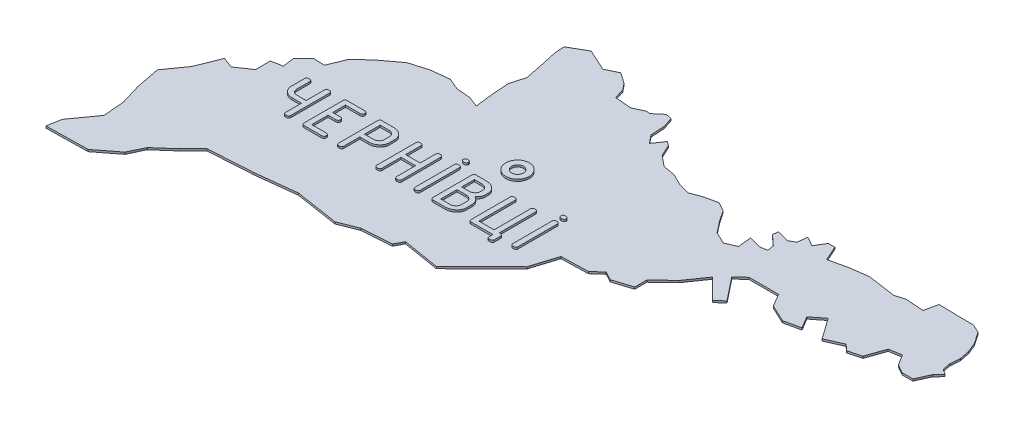
SolidWorks part; units mm, degrees
ref_plane "Спереди" through (0, 0, 0) normal (0, 0, 1) x (1, 0, 0)
ref_plane "Сверху" through (0, 0, 0) normal (0, 1, 0) x (1, 0, 0)
ref_plane "Справа" through (0, 0, 0) normal (1, 0, 0) x (0, 0, -1)
sketch "Эскиз1" plane through (0, 0, 0) normal (0, 1, 0) x (1, 0, 0)
  line B0 (-5205.415, 3609.1673) -> (-5161.2724, 3670.7877)
  line B1 (-5161.2724, 3670.7877) -> (-5165.8164, 3725.3443)
  line B2 (-5165.8164, 3725.3443) -> (-5181.3993, 3776.5482)
  line B3 (-5181.3993, 3776.5482) -> (-5193.7234, 3839.5402)
  line B4 (-5193.7234, 3839.5402) -> (-5157.3862, 3890.7949)
  line B5 (-5157.3862, 3890.7949) -> (-5133.3578, 3950.5103)
  line B6 (-5133.3578, 3950.5103) -> (-5106.1188, 3940.1166)
  line B7 (-5106.1188, 3940.1166) -> (-5069.1288, 3965.4251)
  line B8 (-5069.1288, 3965.4251) -> (-5069.1288, 4003.0603)
  line B9 (-5069.1288, 4003.0603) -> (-5053.5586, 4006.3115)
  line B10 (-5053.5586, 4006.3115) -> (-5041.2193, 4008.2699)
  line B11 (-5041.2193, 4008.2699) -> (-5045.1055, 4038.7626)
  line B12 (-5045.1055, 4038.7626) -> (-5019.1467, 4064.0711)
  line B13 (-5019.1467, 4064.0711) -> (-4990.6022, 4062.7757)
  line B14 (-4990.6022, 4062.7757) -> (-4973.0711, 4106.8879)
  line B15 (-4973.0711, 4106.8879) -> (-4937.3866, 4139.311)
  line B16 (-4937.3866, 4139.311) -> (-4891.3237, 4173.7178)
  line B17 (-4891.3237, 4173.7178) -> (-4845.238, 4187.3627)
  line B18 (-4845.238, 4187.3627) -> (-4799.17, 4192.5469)
  line B19 (-4799.17, 4192.5469) -> (-4769.9651, 4180.2228)
  line B20 (-4769.9651, 4180.2228) -> (-4734.2781, 4176.997)
  line B21 (-4734.2781, 4176.997) -> (-4707.0188, 4166.6033)
  line B22 (-4707.0188, 4166.6033) -> (-4712.2105, 4211.3784)
  line B23 (-4712.2105, 4211.3784) -> (-4715.4592, 4257.4464)
  line B24 (-4715.4592, 4257.4464) -> (-4705.063, 4294.4186)
  line B25 (-4705.063, 4294.4186) -> (-4714.1587, 4339.1938)
  line B26 (-4714.1587, 4339.1938) -> (-4723.8818, 4383.3313)
  line B27 (-4723.8818, 4383.3313) -> (-4725.8453, 4409.3028)
  line B28 (-4725.8453, 4409.3028) -> (-4681.7153, 4434.6114)
  line B29 (-4681.7153, 4434.6114) -> (-4626.5617, 4409.3028)
  line B30 (-4626.5617, 4409.3028) -> (-4596.0411, 4424.2177)
  line B31 (-4596.0411, 4424.2177) -> (-4568.7844, 4405.4141)
  line B32 (-4568.7844, 4405.4141) -> (-4555.1446, 4388.5409)
  line B33 (-4555.1446, 4388.5409) -> (-4548.0122, 4363.2069)
  line B34 (-4548.0122, 4363.2069) -> (-4505.8432, 4359.3182)
  line B35 (-4505.8432, 4359.3182) -> (-4479.8844, 4371.6677)
  line B36 (-4479.8844, 4371.6677) -> (-4468.2156, 4371.6677)
  line B37 (-4468.2156, 4371.6677) -> (-4446.1532, 4390.4713)
  line B38 (-4446.1532, 4390.4713) -> (-4430.5677, 4387.2455)
  line B39 (-4430.5677, 4387.2455) -> (-4422.1451, 4361.2765)
  line B40 (-4422.1451, 4361.2765) -> (-4420.1969, 4325.5743)
  line B41 (-4420.1969, 4325.5743) -> (-4403.3237, 4304.8123)
  line B42 (-4403.3237, 4304.8123) -> (-4384.5074, 4332.0792)
  line B43 (-4384.5074, 4332.0792) -> (-4374.1061, 4323.6413)
  line B44 (-4374.1061, 4323.6413) -> (-4360.5044, 4294.4186)
  line B45 (-4360.5044, 4294.4186) -> (-4333.2375, 4272.3638)
  line B46 (-4333.2375, 4272.3638) -> (-4302.7194, 4267.1797)
  line B47 (-4302.7194, 4267.1797) -> (-4275.4779, 4253.5348)
  line B48 (-4275.4779, 4253.5348) -> (-4244.3248, 4245.0969)
  line B49 (-4244.3248, 4245.0969) -> (-4215.765, 4255.516)
  line B50 (-4215.765, 4255.516) -> (-4183.314, 4262.6305)
  line B51 (-4183.314, 4262.6305) -> (-4160.6216, 4250.3065)
  line B52 (-4160.6216, 4250.3065) -> (-4142.453, 4223.0396)
  line B53 (-4142.453, 4223.0396) -> (-4119.7352, 4193.8702)
  line B54 (-4119.7352, 4193.8702) -> (-4089.2425, 4178.9274)
  line B55 (-4089.2425, 4178.9274) -> (-4061.9782, 4190.6165)
  line B56 (-4061.9782, 4190.6165) -> (-4065.2294, 4224.9979)
  line B57 (-4065.2294, 4224.9979) -> (-4034.7367, 4216.56)
  line B58 (-4034.7367, 4216.56) -> (-4015.8822, 4219.8138)
  line B59 (-4015.8822, 4219.8138) -> (-4019.136, 4236.687)
  line B60 (-4019.136, 4236.687) -> (-4045.1049, 4260.6747)
  line B61 (-4045.1049, 4260.6747) -> (-4043.1491, 4274.3196)
  line B62 (-4043.1491, 4274.3196) -> (-4012.6564, 4265.8843)
  line B63 (-4012.6564, 4265.8843) -> (-3997.0786, 4274.3196)
  line B64 (-3997.0786, 4274.3196) -> (-3993.8249, 4299.6282)
  line B65 (-3993.8249, 4299.6282) -> (-3969.8117, 4286.0087)
  line B66 (-3969.8117, 4286.0087) -> (-3954.2364, 4311.9777)
  line B67 (-3954.2364, 4311.9777) -> (-3937.3886, 4311.9777)
  line B68 (-3937.3886, 4311.9777) -> (-3920.49, 4274.3196)
  line B69 (-3920.49, 4274.3196) -> (-3874.4449, 4284.7133)
  line B70 (-3874.4449, 4284.7133) -> (-3828.3515, 4291.1674)
  line B71 (-3828.3515, 4291.1674) -> (-3792.0143, 4286.0087)
  line B72 (-3792.0143, 4286.0087) -> (-3756.3374, 4280.7992)
  line B73 (-3756.3374, 4280.7992) -> (-3731.0263, 4287.9391)
  line B74 (-3731.0263, 4287.9391) -> (-3684.9583, 4284.7133)
  line B75 (-3684.9583, 4284.7133) -> (-3677.793, 4318.4572)
  line B76 (-3677.793, 4318.4572) -> (-3621.3542, 4317.1364)
  line B77 (-3621.3542, 4317.1364) -> (-3588.9057, 4317.1364)
  line B78 (-3588.9057, 4317.1364) -> (-3566.8229, 4306.7681)
  line B79 (-3566.8229, 4306.7681) -> (-3546.7239, 4277.548)
  line B80 (-3546.7239, 4277.548) -> (-3536.3302, 4252.2623)
  line B81 (-3536.3302, 4252.2623) -> (-3531.1715, 4226.2933)
  line B82 (-3531.1715, 4226.2933) -> (-3533.1019, 4200.9847)
  line B83 (-3533.1019, 4200.9847) -> (-3529.1903, 4180.2228)
  line B84 (-3529.1903, 4180.2228) -> (-3515.5683, 4171.7874)
  line B85 (-3515.5683, 4171.7874) -> (-3531.1715, 4154.9142)
  line B86 (-3531.1715, 4154.9142) -> (-3546.7239, 4120.5074)
  line B87 (-3546.7239, 4120.5074) -> (-3573.9629, 4120.5074)
  line B88 (-3573.9629, 4120.5074) -> (-3596.0202, 4132.8315)
  line B89 (-3596.0202, 4132.8315) -> (-3612.9189, 4160.0984)
  line B90 (-3612.9189, 4160.0984) -> (-3644.0466, 4154.9142)
  line B91 (-3644.0466, 4154.9142) -> (-3660.9198, 4106.8879)
  line B92 (-3660.9198, 4106.8879) -> (-3693.3683, 4098.4526)
  line B93 (-3693.3683, 4098.4526) -> (-3708.9715, 4112.0974)
  line B94 (-3708.9715, 4112.0974) -> (-3751.1279, 4093.2938)
  line B95 (-3751.1279, 4093.2938) -> (-3788.7859, 4146.4789)
  line B96 (-3788.7859, 4146.4789) -> (-3819.2786, 4122.4657)
  line B97 (-3819.2786, 4122.4657) -> (-3801.0846, 4091.9476)
  line B98 (-3801.0846, 4091.9476) -> (-3841.971, 4082.8747)
  line B99 (-3841.971, 4082.8747) -> (-3886.1086, 4103.6342)
  line B100 (-3886.1086, 4103.6342) -> (-3904.9401, 4136.0852)
  line B101 (-3904.9401, 4136.0852) -> (-3980.2054, 4136.0852)
  line B102 (-3980.2054, 4136.0852) -> (-4003.5582, 4115.3232)
  line B103 (-4003.5582, 4115.3232) -> (-3956.1922, 4055.6078)
  line B104 (-3956.1922, 4055.6078) -> (-3976.3167, 4038.7626)
  line B105 (-3976.3167, 4038.7626) -> (-4027.5713, 4090.0147)
  line B106 (-4027.5713, 4090.0147) -> (-4061.9782, 4040.693)
  line B107 (-4061.9782, 4040.693) -> (-4104.7949, 3999.8066)
  line B108 (-4104.7949, 3999.8066) -> (-4104.7949, 3968.6535)
  line B109 (-4104.7949, 3968.6535) -> (-4152.1609, 3953.7361)
  line B110 (-4152.1609, 3953.7361) -> (-4174.2436, 3965.4251)
  line B111 (-4174.2436, 3965.4251) -> (-4198.2568, 3944.0053)
  line B112 (-4198.2568, 3944.0053) -> (-4266.3821, 3942.0724)
  line B113 (-4266.3821, 3942.0724) -> (-4287.1415, 3875.8774)
  line B114 (-4287.1415, 3875.8774) -> (-4403.3237, 3760.9958)
  line B115 (-4403.3237, 3760.9958) -> (-4497.4154, 3776.5482)
  line B116 (-4497.4154, 3776.5482) -> (-4509.0918, 3754.5162)
  line B117 (-4509.0918, 3754.5162) -> (-4584.3571, 3749.3321)
  line B118 (-4584.3571, 3749.3321) -> (-4631.7433, 3730.5031)
  line B119 (-4631.7433, 3730.5031) -> (-4741.4129, 3747.3763)
  line B120 (-4741.4129, 3747.3763) -> (-4843.2923, 3735.7126)
  line B121 (-4843.2923, 3735.7126) -> (-4956.1877, 3728.5727)
  line B122 (-4956.1877, 3728.5727) -> (-4991.9026, 3692.8704)
  line B123 (-4991.9026, 3692.8704) -> (-5034.727, 3655.2099)
  line B124 (-5034.727, 3655.2099) -> (-5053.5586, 3616.3072)
  line B125 (-5053.5586, 3616.3072) -> (-5106.1188, 3575.4208)
  line B126 (-5106.1188, 3575.4208) -> (-5211.8819, 3573.4904)
  line B127 (-5211.8819, 3573.4904) -> (-5205.415, 3609.1673)
sketch_block_instance "Блок8-1"
sketch_block "Блок8"
extrude "Бобышка-Вытянуть1" add sketch "Эскиз1" along normal blind 5 contours B127 B126 B125 B124 B123 B122 B121 B120 B119 B118 B117 B116 B115 B114 B113 B112 B111 B110 B109 B108 B107 B106 B105 B104 B103 B102 B101 B100 B99 B98 B97 B96 B95 B94 B93 B92 B91 B90 B89 B88 B87 B86 B85 B84 B83 B82 B81 B80 B79 B78 B77
sketch "Эскиз2" plane through (0, 0, 0) normal (0, 1, 0) x (1, 0, 0)
  line L0 (-4990.6641, 3898.6682) -> (-3956.0852, 3898.6682) construction
  circle A0 centre (-4508.7755, 4073.7293) radius 15
  circle A1 centre (-4508.7755, 4073.7293) radius 30
  text T0 "<b>ЧЕРНІВЦІ</b>" font "GOST Type AU" height 110
  dimension "D1" = 30
  dimension "D2" = 60
extrude "Бобышка-Вытянуть2" add sketch "Эскиз2" along normal blind 10
scale "Масштаб1" scale about centroid uniform scaling yes scale factor 0.05
